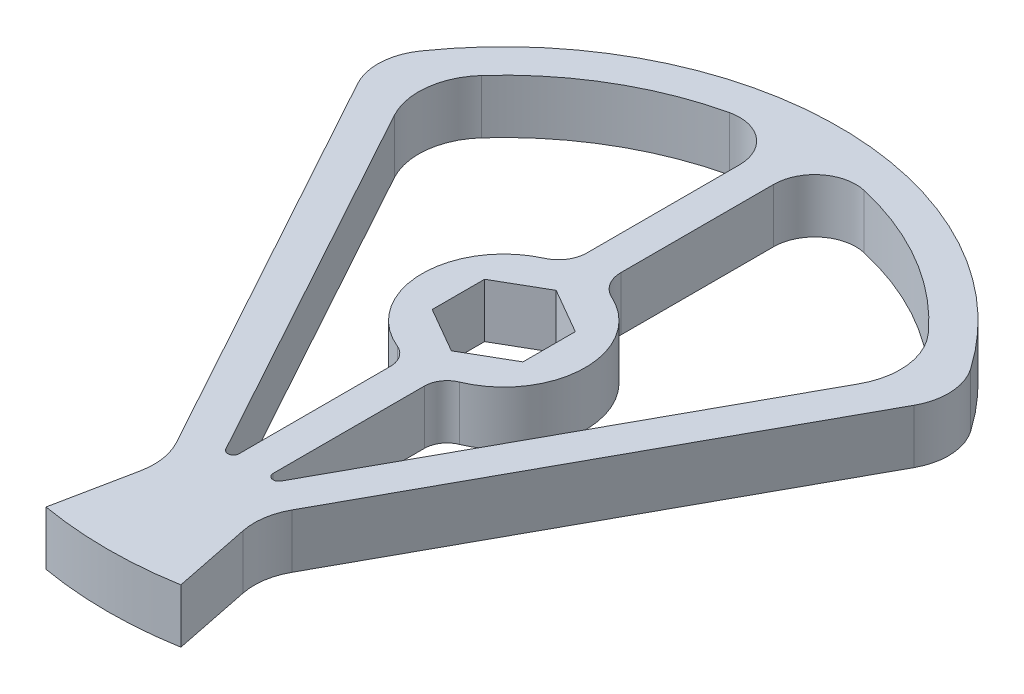
SolidWorks part; units mm, degrees
other "Markup1"
sketch "Sketch4" plane through (50.347, 12.7, 76.2516) normal (0.2252, 0.9055, 0.3597) x (0.9613, -0.2666, 0.0691)
material "1023 Carbon Steel Sheet (SS)"
ref_plane "Front Plane" through (0, 0, 0) normal (0, 0, 1) x (1, 0, 0)
ref_plane "Top Plane" through (0, 0, 0) normal (0, 1, 0) x (1, 0, 0)
ref_plane "Right Plane" through (0, 0, 0) normal (1, 0, 0) x (0, 0, -1)
other "Center of Mass"
sketch "Sketch1" plane through (0, 0, 0) normal (0, 1, 0) x (1, 0, 0)
  line L0 (-5.08, 6.1801) -> (-3.6243, 7.1451)
  line L1 (0, 9.2376) -> (-8, 4.6188)
  line L2 (-8, 4.6188) -> (-8, -4.6188)
  line L3 (-8, -4.6188) -> (0, -9.2376)
  line L4 (0, -9.2376) -> (8, -4.6188)
  line L5 (8, -4.6188) -> (8, 4.6188)
  line L6 (8, 4.6188) -> (0, 9.2376)
  line L8 (0, -9.2376) -> (0, -8)
  line L9 (5.08, -6.3047) -> (5.08, -6.1801)
  line L10 (5.08, 6.1801) -> (5.08, 6.3047)
  line L11 (0, 0) -> (0, -44.5575) construction
  line L12 (-7, -3.873) -> (-7, -5.1962)
  line L13 (-44.7107, 28.4739) -> (-3, -47.565)
  line L14 (3.2, 7.3321) -> (4.7257, 6.5092)
  line L16 (-3.2, 7.3321) -> (-1.2743, 8.5019)
  line L18 (0, 8) -> (0, 9.2376)
  line L22 (-8.291, -51.039) -> (-51.8754, 28.4157)
  line L25 (8.3097, -51.1314) -> (51.9101, 28.3523)
  line L33 (-7, 0) -> (-7, -74.4679) construction
  line L37 (44.7107, 28.4739) -> (3, -47.565)
  line L40 (4, -41.5834) -> (4, -13.8093) construction
  line L41 (-4, -41.5834) -> (-4, -13.8093) construction
  line L42 (4, 13.8093) -> (4, 52.8565) construction
  line L43 (-45.802, 30.4633) -> (-2, -49.388) construction
  line L44 (-2, -49.388) -> (-2, -12.2142) construction
  line L45 (0, 0) -> (0, -74.4679) construction
  line L46 (2, -49.388) -> (2, -12.2142) construction
  line L47 (45.802, 30.4633) -> (2, -49.388) construction
  line L48 (43.4589, 30.3503) -> (4, -41.5834) construction
  line L49 (-43.4589, 30.3503) -> (-4, -41.5834) construction
  line L50 (-2, 12.2142) -> (-2, 54.9713) construction
  line L51 (2, 12.2142) -> (2, 54.9713) construction
  line L52 (-3, 14.0604) -> (-3, 52.9227)
  line L55 (3, 14.0604) -> (3, 52.9227)
  line L58 (-45.8703, 28.5086) -> (-3, -49.6442) construction
  line L59 (-3, -49.6442) -> (-3, -13.0362) construction
  line L60 (3, -49.6442) -> (3, -13.0362) construction
  line L61 (45.8703, 28.5086) -> (3, -49.6442) construction
  line L62 (-3, 13.0362) -> (-3, 53.9243) construction
  line L63 (3, 13.0362) -> (3, 53.9243) construction
  line L64 (-4, 13.8093) -> (-4, 52.8565) construction
  line L65 (4, 13.8093) -> (4, 52.8565) construction
  line L66 (-3, -47.565) -> (-3, -13.8093)
  line L67 (3, -47.565) -> (3, -13.8093)
  line L68 (4, -45.742) -> (4, -13.8093) construction
  line L70 (-44.7107, 28.4739) -> (-4, -45.742) construction
  line L71 (44.7107, 28.4739) -> (4, -45.742) construction
  line L72 (-4, -45.742) -> (-4, -13.8093) construction
  line L76 (-12.8768, -68.6528) -> (-12.8782, -68.6598)
  line L77 (-9.0363, -49.6803) -> (-12.8782, -68.6598) construction
  line L78 (8.3097, -51.1314) -> (11.8981, -68.8582)
  line L79 (12.8768, -68.6528) -> (12.8782, -68.6598)
  line L80 (-8.291, -51.039) -> (-11.8981, -68.8582)
  line L81 (-8.0561, -49.8787) -> (-11.8981, -68.8582) construction
  line L82 (9.055, -49.7728) -> (12.8782, -68.6598) construction
  line L83 (8.0749, -49.9712) -> (11.8981, -68.8582) construction
  arc A0 (-3, 14.0604) -> (-3, -14.0604) centre (0, 0) ccw
  circle A1 centre (0, 0) radius 8 construction
  arc A5 (46.133, 37.3508) -> (-46.133, 37.3508) centre (0, 0) ccw
  arc A12 (3, -14.0604) -> (3, 14.0604) centre (0, 0) ccw
  arc A15 (-3, 52.9227) -> (-44.7107, 28.4739) centre (0, 0) ccw
  arc A18 (51.9101, 28.3523) -> (-51.8754, 28.4157) centre (0, 0) ccw
  arc A20 (44.7107, 28.4739) -> (3, 52.9227) centre (0, 0) ccw
  arc A26 (2, -12.2142) -> (2, 12.2142) centre (0, 0) ccw construction
  arc A27 (-2, 12.2142) -> (-2, -12.2142) centre (0, 0) ccw construction
  arc A28 (-4, 52.8565) -> (-43.4589, 30.3503) centre (0, 0) ccw construction
  arc A29 (43.4589, 30.3503) -> (4, 52.8565) centre (0, 0) ccw construction
  arc A30 (-2, 54.9713) -> (-45.802, 30.4633) centre (0, 0) ccw construction
  arc A31 (45.802, 30.4633) -> (2, 54.9713) centre (0, 0) ccw construction
  arc A36 (-3, 13.0362) -> (-3, -13.0362) centre (0, 0) ccw construction
  arc A37 (-3, 53.9243) -> (-45.8703, 28.5086) centre (0, 0) ccw construction
  arc A38 (3, -13.0362) -> (3, 13.0362) centre (0, 0) ccw construction
  arc A39 (45.8703, 28.5086) -> (3, 53.9243) centre (0, 0) ccw construction
  arc A40 (-4, 52.8565) -> (-44.7107, 28.4739) centre (0, 0) ccw construction
  arc A41 (44.7107, 28.4739) -> (4, 52.8565) centre (0, 0) ccw construction
  arc A42 (-4, 13.8093) -> (-4, -13.8093) centre (0, 0) ccw construction
  arc A43 (4, -13.8093) -> (4, 13.8093) centre (0, 0) ccw construction
  arc A46 (-11.8924, -68.8302) -> (11.8924, -68.8302) centre (0, 0) ccw
  dimension "D1" = 16
  dimension "D2" = 1
  dimension "D3" = 1
  dimension "D4" = 1
  dimension "D6" = 2
extrude "Boss-Extrude5" add sketch "Sketch1" along normal blind 9.525 contours L25 A18 A5 L22 L6 L5 L4 L3 L2 L1 A15 A0 L13 A20 L37 A12 region at (-28.6316, 0, 10.5154)
fillet "Fillet8" radius 5 2 edges at (-3, 4.7625, -14.0604) (3, 4.7625, -14.0604)
fillet "Fillet9" radius 7.25 2 edges at (-3, 4.7625, -52.9227) (3, 4.7625, -52.9227)
fillet "Fillet10" radius 4 2 edges at (-3, 4.7625, 14.0604) (3, 4.7625, 14.0604)
fillet "Fillet11" radius 1 2 edges at (-3, 4.7625, 47.565) (3, 4.7625, 47.565)
fillet "Fillet14" radius 12 2 edges at (44.7107, 4.7625, -28.4739) (-44.7107, 4.7625, -28.4739)
fillet "Fillet15" radius 10 2 edges at (51.9101, 4.7625, -28.3523) (-51.8754, 4.7625, -28.4157)
fillet "Fillet16" radius 11 2 edges at (-8.291, 4.7625, 51.039) (8.3097, 4.7625, 51.1314)
